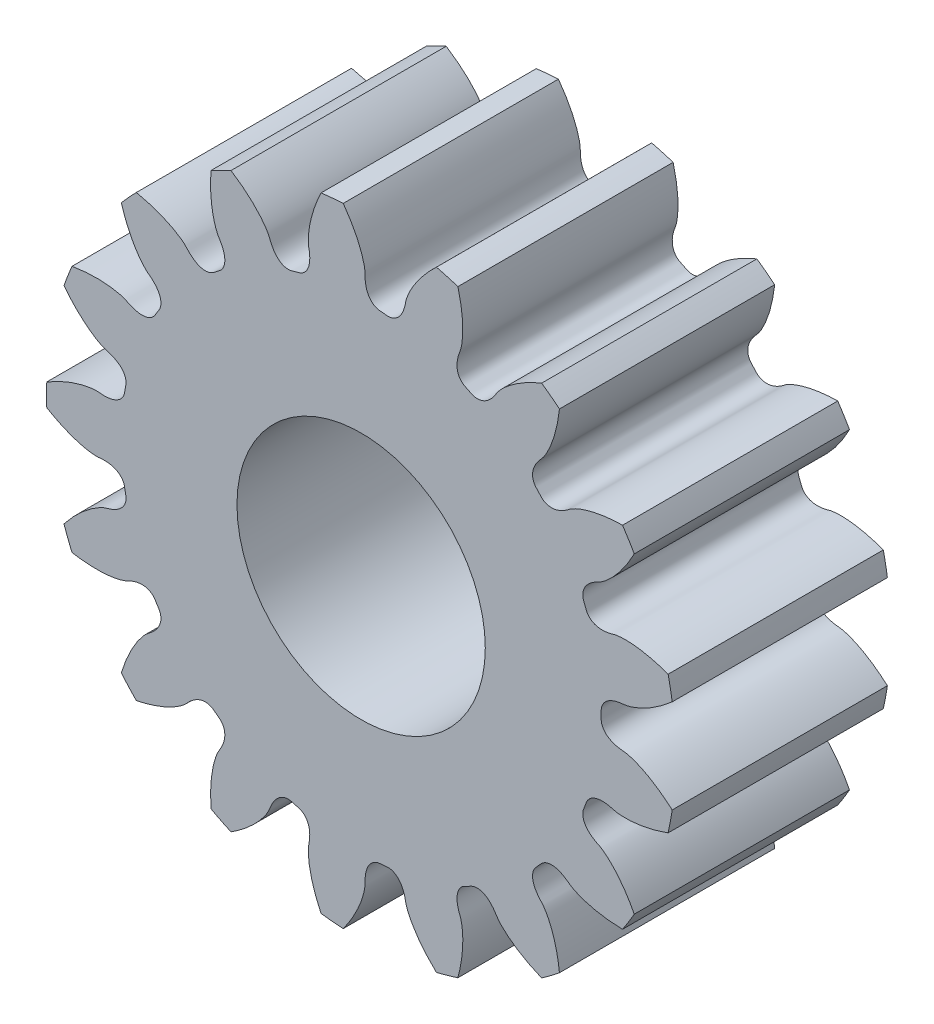
SolidWorks part; units mm, degrees
ref_plane "Front Plane" through (0, 0, 0) normal (0, 0, 1) x (1, 0, 0)
ref_plane "Top Plane" through (0, 0, 0) normal (0, 1, 0) x (1, 0, 0)
ref_plane "Right Plane" through (0, 0, 0) normal (1, 0, 0) x (0, 0, -1)
ref_axis "Axis1" through (0, 0, 55) along (0, 0, -1)
sketch "旋转草图小直齿轮" plane through (0, 0, 0) normal (1, 0, 0) x (0, 0, -1)
  line L0 (0, 0) -> (1, 0) construction
  line L1 (-10, 0) -> (-10, 19)
  line L2 (-10, 19) -> (3, 19)
  line L3 (3, 19) -> (3, 0)
  line L4 (3, 0) -> (-10, 0)
  dimension "Side1" = 10
  dimension "OutsideRadius" = 19
  dimension "Side2" = 3
revolve "小直齿轮" add sketch "旋转草图小直齿轮" angle 360 about L0
sketch "齿草图小直齿轮" plane through (0, 0, 0) normal (0, 0, 1) x (1, 0, 0)
  arc A0 (18.8777, 2.9059) -> (18.8777, -2.9059) centre (0, 0) cw
  spline S0 degree 3 poles (18.8777, -2.9059) (18.7162, -2.7605) (18.4737, -2.5555) (18.1462, -2.3058) (17.9156, -2.1416) (17.694, -1.9946) (17.4824, -1.8638) (17.2814, -1.7487) (17.092, -1.6481) (16.9148, -1.5614) (16.7504, -1.4876) (16.5997, -1.4257) (16.463, -1.3747) (16.3411, -1.3337) (16.2343, -1.3016) (16.143, -1.2774) (16.0678, -1.2601) (16.0089, -1.2485) (15.9082, -1.2318) (15.8073, -1.2291) (15.7037, -1.216) (15.6495, -1.2083) (15.5963, -1.1996) (15.544, -1.19) (15.4927, -1.1794) (15.4423, -1.1677) (15.3928, -1.1551) (15.3442, -1.1414) (15.2965, -1.1266) (15.2496, -1.1108) (15.2035, -1.0937) (15.1582, -1.0755) (15.1136, -1.056) (15.0698, -1.0351) (15.0267, -1.0127) (14.9843, -0.9888) (14.9426, -0.9632) (14.9016, -0.9357) (14.8613, -0.9062) (14.8218, -0.8744) (14.7832, -0.8402) (14.7455, -0.8034) (14.709, -0.7636) (14.674, -0.7206) (14.6407, -0.6743) (14.6095, -0.6245) (14.581, -0.5711) (14.5558, -0.5142) (14.5343, -0.4538) (14.5174, -0.3904) (14.5054, -0.3246) (14.4997, -0.2626) (14.4972, -0.1542) (14.5022, 0) (14.4972, 0.1542) (14.4997, 0.2626) (14.5054, 0.3246) (14.5174, 0.3904) (14.5343, 0.4538) (14.5558, 0.5142) (14.581, 0.5711) (14.6095, 0.6245) (14.6407, 0.6743) (14.674, 0.7206) (14.709, 0.7636) (14.7455, 0.8034) (14.7832, 0.8402) (14.8218, 0.8744) (14.8613, 0.9062) (14.9016, 0.9357) (14.9426, 0.9632) (14.9843, 0.9888) (15.0267, 1.0127) (15.0698, 1.0351) (15.1136, 1.056) (15.1582, 1.0755) (15.2035, 1.0937) (15.2496, 1.1108) (15.2965, 1.1266) (15.3442, 1.1414) (15.3928, 1.1551) (15.4423, 1.1677) (15.4927, 1.1794) (15.544, 1.19) (15.5963, 1.1996) (15.6495, 1.2083) (15.7037, 1.216) (15.8073, 1.2291) (15.9082, 1.2318) (16.0089, 1.2485) (16.0678, 1.2601) (16.143, 1.2774) (16.2343, 1.3016) (16.3411, 1.3337) (16.463, 1.3747) (16.5997, 1.4257) (16.7504, 1.4876) (16.9148, 1.5614) (17.092, 1.6481) (17.2814, 1.7487) (17.4824, 1.8638) (17.694, 1.9946) (17.9156, 2.1416) (18.1462, 2.3058) (18.4737, 2.5555) (18.7162, 2.7605) (18.8777, 2.9059) knots 0 0 0 0 0.058344 0.085213 0.110547 0.134345 0.156608 0.177336 0.196528 0.214185 0.230306 0.244893 0.257943 0.269459 0.279439 0.287883 0.294792 0.300166 0.304005 0.32219 0.327162 0.332059 0.336883 0.341638 0.346326 0.350953 0.355523 0.36004 0.36451 0.36894 0.373335 0.377703 0.382053 0.386393 0.390734 0.395086 0.399462 0.403875 0.408338 0.412867 0.417479 0.422188 0.427012 0.431965 0.437063 0.442315 0.447728 0.453304 0.459035 0.464908 0.470898 0.476975 0.481621 0.5 0.518379 0.523025 0.529102 0.535092 0.540965 0.546696 0.552272 0.557685 0.562937 0.568035 0.572988 0.577812 0.582521 0.587133 0.591662 0.596125 0.600538 0.604914 0.609266 0.613607 0.617947 0.622297 0.626665 0.63106 0.63549 0.63996 0.644477 0.649047 0.653674 0.658362 0.663117 0.667941 0.672838 0.67781 0.695995 0.699834 0.705208 0.712117 0.720561 0.730541 0.742057 0.755107 0.769694 0.785815 0.803472 0.822664 0.843392 0.865655 0.889453 0.914787 0.941656 1 1 1 1
extrude "齿拉伸切除小直齿轮" cut sketch "齿草图小直齿轮" against normal blind 10 and the other way blind 10
pattern_circular "齿形小直齿轮" count 17 every 21.176 about axis through (0, 0, 55) along (0, 0, -1) of "齿拉伸切除小直齿轮"
sketch "孔旋转草图" plane through (0, 0, 0) normal (1, 0, 0) x (0, 0, -1)
  line L0 (0, 0) -> (1, 0) construction
  line L1 (-10, 0) -> (10, 0)
  line L2 (10, 0) -> (10, 7.5)
  line L3 (10, 7.5) -> (-10, 7.5)
  line L4 (-10, 7.5) -> (-10, 0)
  dimension "BoreSide1" = 10
  dimension "TaperSide1" = 7.5
  dimension "BoreSide2" = 10
  dimension "TaperSide2" = 7.5
revolve "孔旋转切除" cut sketch "孔旋转草图" angle 360 about L0
sketch "辅助草图小直齿轮" plane through (0, 0, 0) normal (0, 0, 1) x (1, 0, 0)
  circle A0 centre (0, 0) radius 17 construction
  circle A1 centre (0, 0) radius 15.9748 construction
  circle A2 centre (0, 0) radius 15.9784 construction
  circle A3 centre (0, 0) radius 19 construction
  circle A4 centre (0, 0) radius 14.5 construction
  dimension "PitchDiameter" = 34
  dimension "BaseDiameter" = 31.9495
  dimension "FormDiameter" = 31.9568
  dimension "MajorDiameter" = 38
  dimension "MinorDiameter" = 29
